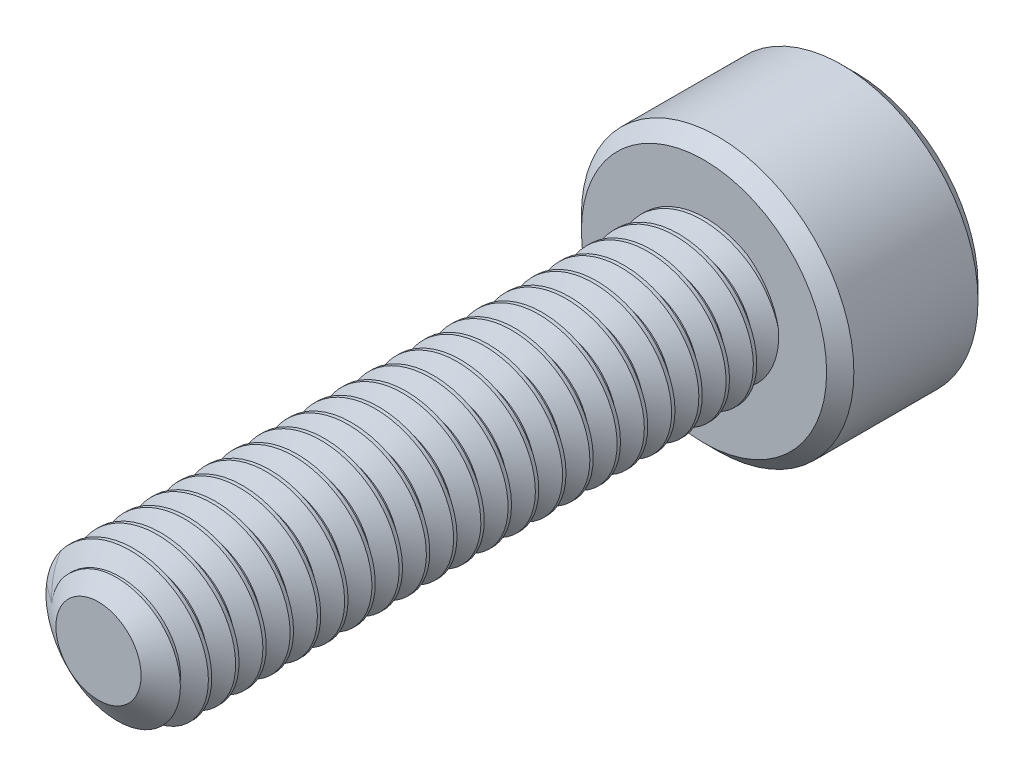
SolidWorks part; units mm, degrees
ref_plane "Front Plane" through (0, 0, 0) normal (0, 0, 1) x (1, 0, 0)
ref_plane "Top Plane" through (0, 0, 0) normal (0, 1, 0) x (1, 0, 0)
ref_plane "Right Plane" through (0, 0, 0) normal (1, 0, 0) x (0, 0, -1)
sketch "Sketch1" plane through (0, 0, 0) normal (0, 0, 1) x (1, 0, 0)
  circle A0 centre (0, 0) radius 1.25
  dimension "OD" = 2.5
extrude "Extrude1" add sketch "Sketch1" against normal blind 10
sketch "Sketch2" plane through (0, 0, 0) normal (0, 0, 1) x (1, 0, 0)
  circle A0 centre (0, 0) radius 1.25 construction
  circle A1 centre (0, 0) radius 1.25
curve "Helix/Spiral1" pitch 0.45 height 10.45 radius 1.25 centre (0, 0, 0) axis (0, 0, -1) start towards (0, 1, 0) parameters "pitch"=0.45
sketch "Sketch3" plane through (0, 0, 0) normal (1, 0, 0) x (0, 0, -1)
  line L0 (-0.3937, 1.25) -> (-0.225, 0.9577)
  line L1 (-0.225, 0.9577) -> (-0.1688, 0.9577)
  line L2 (-0.1688, 0.9577) -> (0, 1.25)
  line L3 (-0.3937, 1.25) -> (0, 1.25)
  line L4 (-0.1969, 1.25) -> (-0.1969, 0.9577) construction
  line L5 (-0.3094, 1.1039) -> (-0.0844, 1.1039) construction
  line L6 (0, 1.25) -> (0, -1.25) construction
  dimension "D1" = 0.0563
  dimension "D2" = 0.225
  dimension "D3" = 60
sweep "Cut-Sweep1" cut profiles "Sketch3" path "Helix/Spiral1" align with end faces yes
sketch "Sketch4" plane through (0, 0, 0) normal (1, 0, 0) x (0, 0, -1)
  line L0 (0.3825, 1.25) -> (0, 0.7037)
  line L1 (0, 0.7037) -> (0, 1.25)
  line L2 (0.3825, 1.25) -> (0, 1.25)
  line L3 (-0.3937, 1.25) -> (0, 1.25) construction
  line L4 (0, 0) -> (7.0209, 0) construction
  dimension "D1" = 55
  dimension "D2" = 0.254
revolve "Cut-Revolve1" cut sketch "Sketch4" angle 360 about L4
sketch "Sketch6" plane through (0, 0, -10) normal (0, 0, -1) x (-1, 0, 0)
  circle A0 centre (0, 0) radius 2.25
  dimension "head dia" = 4.5
extrude "Extrude2" add sketch "Sketch6" along normal blind 2.5
sketch "Sketch7" plane through (0, 0, -12.5) normal (0, 0, -1) x (-1, 0, 0)
  line L1 (0, 1.1547) -> (-1, 0.5774)
  line L2 (-1, 0.5774) -> (-1, -0.5774)
  line L3 (-1, -0.5774) -> (0, -1.1547)
  line L4 (0, -1.1547) -> (1, -0.5774)
  line L5 (1, -0.5774) -> (1, 0.5774)
  line L6 (1, 0.5774) -> (0, 1.1547)
  circle A0 centre (0, 0) radius 1 construction
  dimension "hex dia" = 2
extrude "Cut-Extrude1" cut sketch "Sketch7" against normal blind 1.5
sketch "Sketch8" plane through (0, 0, -12.5) normal (0, 0, -1) x (-1, 0, 0)
  circle A0 centre (0, 0) radius 1.1547
extrude "Cut-Extrude2" cut sketch "Sketch8" against normal through all draft 45
chamfer "Chamfer1" distance 0.225 angle 45 2 edges at (-2.25, 0, -12.5) (-2.25, 0, -10)
sketch "Sketch10" plane through (0, 0, -10) normal (0, 0, 1) x (1, 0, 0)
  circle A1 centre (0, 0) radius 1.25
  circle A2 centre (0, 0) radius 1.25
  dimension "D1" = 0
ref_plane "Plane1" through (0, 0, 0) normal (0, 0, 1) x (1, 0, 0)
extrude "partial thread" [suppressed] add sketch "Sketch10" along normal up to surface (8 mm away) separate body up to plane "Plane1"
chamfer "Chamfer2" [suppressed] distance 0.05 angle 45
combine bodies "Combine1" [suppressed] operation type add bodies to combine 107 108
sketch "Sketch9" plane through (0, 0, 0) normal (1, 0, 0) x (0, 0, -1)
  line L0 (0, 1.25) -> (0, -1.25) construction
  line L1 (1.125, 1.25) -> (1.125, -1.25) construction
  dimension "D1" = 1.125
equation "\"D3@Helix/Spiral1\" = \"screw length@Extrude1\"+\"pitch@Helix/Spiral1\""
equation "\"D1@Sketch3\" = \"pitch@Helix/Spiral1\"*.125"
equation "\"D2@Sketch3\" = \"pitch@Helix/Spiral1\"*.5"
equation "\"D1@Cut-Extrude1\" = \"hex dia@Sketch7\"*.75"
equation "\"D1@Chamfer1\" = \"head dia@Sketch6\"*.05"
equation "\"D1@Sketch9\" = \"pitch@Helix/Spiral1\"*2.5"
equation "\"D1@Chamfer2\"=\"OD@Sketch1\"*.02"
